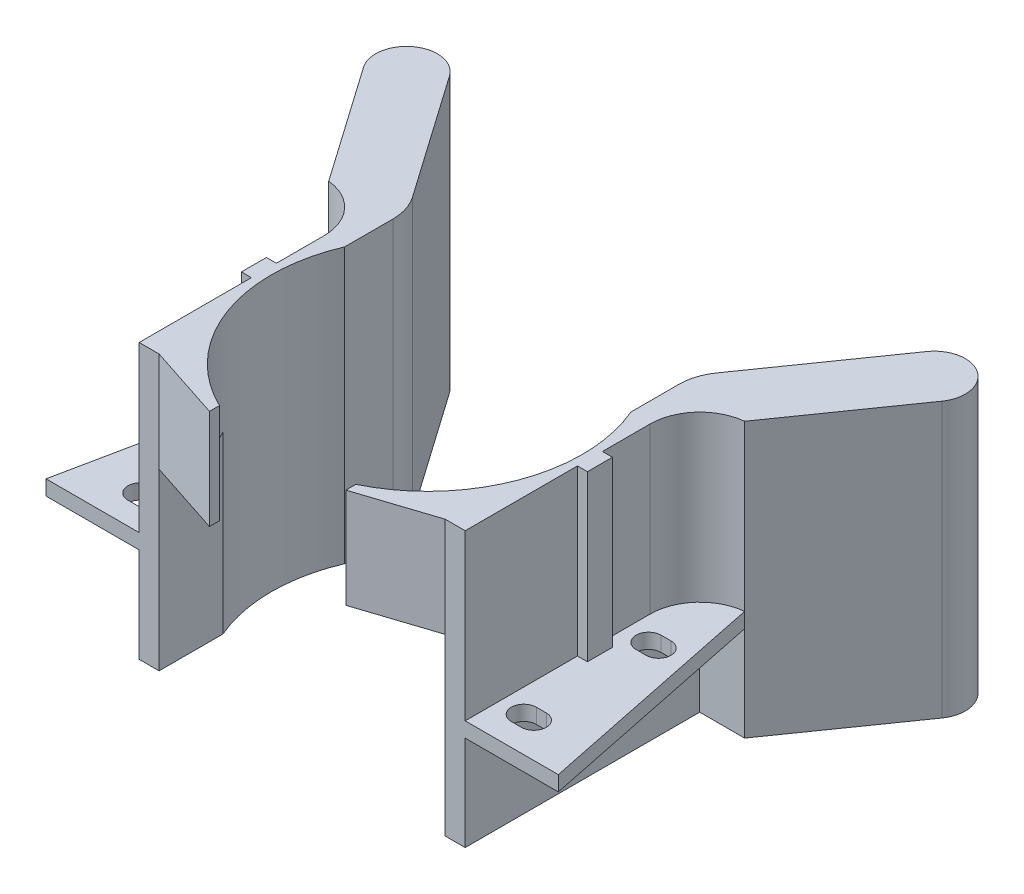
SolidWorks part; units mm, degrees
ref_plane "Plan de face" through (0, 0, 0) normal (0, 0, 1) x (1, 0, 0)
ref_plane "Plan de dessus" through (0, 0, 0) normal (0, 1, 0) x (1, 0, 0)
ref_plane "Plan de droite" through (0, 0, 0) normal (1, 0, 0) x (0, 0, -1)
sketch "Esquisse1" plane through (0, 20, 0) normal (0, 1, 0) x (1, 0, 0)
  line L0 (32.6736, -8.5809) -> (32.6736, 38.4191)
  line L1 (32.6736, 38.4191) -> (41.6736, 38.4191)
  line L2 (41.6736, 38.4191) -> (57.9658, 61.6867)
  line L3 (32.6736, -8.5809) -> (28.6736, -8.5809)
  line L4 (28.6736, -8.5809) -> (28.6736, 41.4191)
  line L5 (28.6736, 41.4191) -> (47.8331, 68.7817)
  line L6 (41.6736, 38.4191) -> (33.6736, 38.4191) construction
  line L7 (32.6736, -11.5809) -> (32.6736, 37.4191) construction
  line L9 (27.6736, -11.5809) -> (32.6736, -11.5809) construction
  arc A0 (57.9658, 61.6867) -> (47.8331, 68.7817) centre (52.8994, 65.2342) ccw
  dimension "D4" = 30
  dimension "D2" = 4
  dimension "D3" = 35
  dimension "D5" = 9
  dimension "D6" = 50
  dimension "D7" = 3
extrude "Boss.-Extru.1" add sketch "Esquisse1" along normal blind 55
fillet "Congé1" radius 10 1 edges at (28.6736, 47.5, -41.4191)
sketch "Esquisse2" plane through (0, 75, 0) normal (0, 1, 0) x (1, 0, 0)
  line L0 (28.6736, 16.4191) -> (0.1736, 16.4191) construction
  line L1 (28.6736, 38.2661) -> (28.6736, -8.5809) construction
  line L2 (28.6736, -8.5809) -> (32.6736, -8.5809) construction
  circle A0 centre (0.1736, 16.4191) radius 31
  dimension "D1" = 62
  dimension "D2" = 25
  dimension "D3" = 2.5
extrude "Enlèv. mat.-Extru.1" cut sketch "Esquisse2" against normal through all
sketch "Esquisse3" plane through (0, 39, 0) normal (0, 1, 0) x (1, 0, 0)
  line L0 (32.6736, -8.5809) -> (32.6736, 38.4191) construction
  line L1 (32.6736, 38.4191) -> (41.6736, 38.4191) construction
  line L2 (32.6736, -8.5809) -> (32.6736, 38.4191)
  line L3 (32.6736, 38.4191) -> (41.6736, 38.4191)
  line L4 (32.6736, -8.5809) -> (51.3416, -8.5809)
  line L5 (58.6154, -43.9416) -> (41.6736, 38.4191) construction
  line L6 (51.3416, -8.5809) -> (41.6736, 38.4191)
  line L7 (37.4236, 23.4191) -> (39.4236, 23.4191) construction
  line L8 (37.4236, 25.9191) -> (39.4236, 25.9191)
  line L9 (37.4236, 20.9191) -> (39.4236, 20.9191)
  line L10 (37.4236, -1.5809) -> (39.4236, -1.5809) construction
  line L11 (37.4236, 0.9191) -> (39.4236, 0.9191)
  line L12 (37.4236, -4.0809) -> (39.4236, -4.0809)
  circle A0 centre (38.4236, 23.4191) radius 2.25 construction
  arc A2 (37.4236, 0.9191) -> (37.4236, -4.0809) centre (37.4236, -1.5809) ccw
  arc A3 (39.4236, -4.0809) -> (39.4236, 0.9191) centre (39.4236, -1.5809) ccw
  arc A4 (37.4236, 25.9191) -> (37.4236, 20.9191) centre (37.4236, 23.4191) ccw
  arc A5 (39.4236, 20.9191) -> (39.4236, 25.9191) centre (39.4236, 23.4191) ccw
  point P6 (38.4236, -1.5809)
  point P14 (38.4236, 23.4191)
  dimension "D1" = 2
  dimension "D2" = 2.5
extrude "Boss.-Extru.2" add sketch "Esquisse3" along normal blind 3
ref_plane "Plan1" through (0, 0, -16.4191) normal (0, 0, 1) x (1, 0, 0)
sketch "Esquisse4" plane through (0, 0, -16.4191) normal (0, 0, 1) x (1, 0, 0)
  line L0 (32.6736, 75) -> (34.6736, 75)
  line L1 (34.6736, 75) -> (34.6736, 42)
  line L2 (32.6736, 42) -> (51.3416, 42) construction
  line L3 (34.6736, 42) -> (32.6736, 42)
  line L4 (32.6736, 42) -> (32.6736, 75)
  dimension "D1" = 2
extrude "Boss.-Extru.3" add sketch "Esquisse4" along normal mid plane 5
fillet "Congé2" radius 10 1 edges at (32.6736, 58.5, -38.4191)
sketch "Esquisse5" plane through (0, 75, 0) normal (0, 1, 0) x (1, 0, 0)
  line L0 (13.6736, -11.487) -> (13.6736, -13.487)
  line L1 (13.6736, -13.487) -> (28.6736, -8.5809)
  line L2 (28.6736, -8.5809) -> (32.6736, -8.5809)
  line L3 (13.6736, 56.9508) -> (13.6736, -58.4849) construction
  line L4 (28.6736, 4.2227) -> (28.6736, -8.5809) construction
  line L5 (28.6736, -8.5809) -> (28.6736, 4.2227) construction
  line L6 (32.6736, -8.5809) -> (32.6736, 4.2227)
  line L7 (32.6736, -8.5809) -> (32.6736, 13.9191) construction
  line L8 (32.6736, 4.2227) -> (28.6736, 4.2227)
  arc A0 (13.6736, -11.487) -> (28.6736, 4.2227) centre (0.1736, 16.4191) ccw construction
  arc A1 (28.6736, 4.2227) -> (28.6736, 28.6154) centre (0.1736, 16.4191) ccw construction
  arc A2 (13.6736, -11.487) -> (28.6736, 4.2227) centre (0.1736, 16.4191) ccw
  dimension "D1" = 2
  dimension "D2" = 15
extrude "Boss.-Extru.4" add sketch "Esquisse5" against normal blind 20
mirror "Symétrie1" about plane through (0, 0, 0) normal (1, 0, 0) of bodies 106 104
